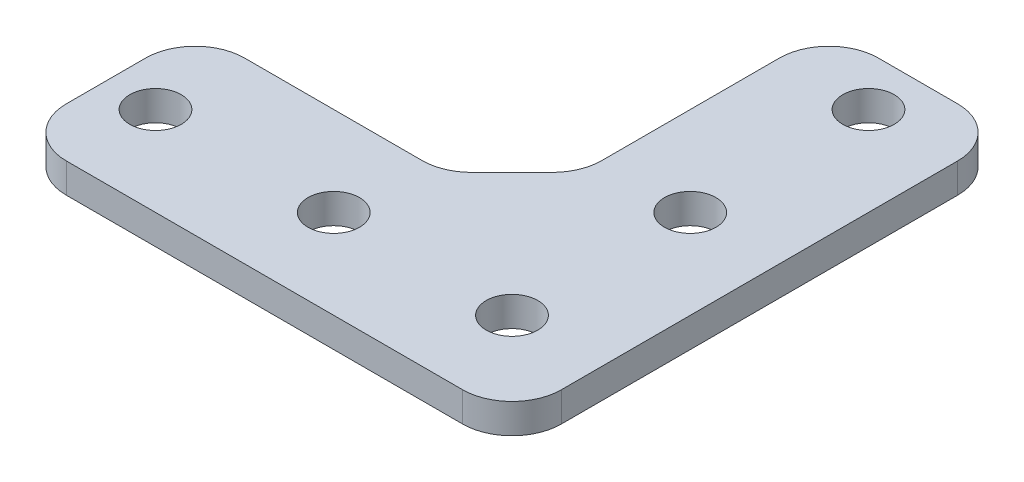
SolidWorks part; units mm, degrees
material "AISI 4340 Steel, annealed"
ref_plane "Front Plane" through (0, 0, 0) normal (0, 0, 1) x (1, 0, 0)
ref_plane "Top Plane" through (0, 0, 0) normal (0, 1, 0) x (1, 0, 0)
ref_plane "Right Plane" through (0, 0, 0) normal (1, 0, 0) x (0, 0, -1)
sketch "Sketch1" plane through (0, 0, 0) normal (0, 1, 0) x (1, 0, 0)
  line L1 (7, 25) -> (25, 25)
  line L2 (-25, -7) -> (-25, -25)
  line L3 (-25, -25) -> (25, -25)
  line L4 (25, 25) -> (25, -25)
  line L5 (-9, 9) -> (25, -25) construction
  line L6 (-25, -25) -> (25, 25) construction
  line L7 (37.4476, -16) -> (-54.2217, -16) construction
  line L8 (7, 48.8177) -> (7, -53.3776) construction
  line L9 (16, 49.9633) -> (16, -43.659) construction
  line L10 (48.8742, -7) -> (-69.3096, -7) construction
  line L14 (7, 25) -> (7, 0)
  line L15 (7, 0) -> (0, -7)
  line L16 (0, -7) -> (-25, -7)
  circle A0 centre (16, -16) radius 2.6
  circle A5 centre (-2, -16) radius 2.6
  circle A6 centre (-20, -16) radius 2.6
  circle A11 centre (16, 2) radius 2.6
  circle A12 centre (16, 20) radius 2.6
  point P0 (0, 0)
  point P34 (7, 25)
  point P37 (-25, -7)
  dimension "D8" = 5.2
  dimension "D9" = 25
  dimension "D10" = 50
  dimension "D11" = 18
  dimension "D6" = 18
  dimension "D7" = 18
  dimension "D12" = 18
  dimension "D13" = 9
  dimension "D1" = 18
  dimension "D2" = 9
  dimension "D3" = 50
  dimension "D4" = 18
  dimension "D5" = 9
  dimension "D14" = 18
  dimension "D15" = 18
  dimension "D16" = 25
  dimension "D17" = 45
base flange "Base-Flange1" sketch "Sketch1" thickness 3 reverse thickness direction no parameters "D1"=3
fillet "Fillet1" radius 5 2 edges at (7, -1.5, 0) (0, -1.5, 7)
fillet "Fillet2" radius 5 5 edges at (25, -1.5, -25) (25, -1.5, 25) (-25, -1.5, 25) (7, -1.5, -25) (-25, -1.5, 7)
sketch "Bend-Lines1" [suppressed] plane through (0, 0, 0) normal (0, 1, 0) x (1, 0, 0)
sketch "Bounding-Box1" [suppressed] plane through (0, 0, 0) normal (0, 1, 0) x (1, 0, 0)
sheet metal parameters "Sheet-Metal4" thickness 3 parameters "D1"=3
flat pattern "Flat-Pattern4" [suppressed]
sketch "Bend-Lines2" plane through (0, 0, 0) normal (0, 1, 0) x (1, 0, 0)
sketch3d "Bounding-Box2" [suppressed]
  line L0 (-25, -25, 0) -> (25, -25, 0) construction
  line L1 (-25, 25, 0) -> (25, 25, 0) construction
  line L2 (-25, -25, 0) -> (-25, 25, 0) construction
  line L3 (25, -25, 0) -> (25, 25, 0) construction
